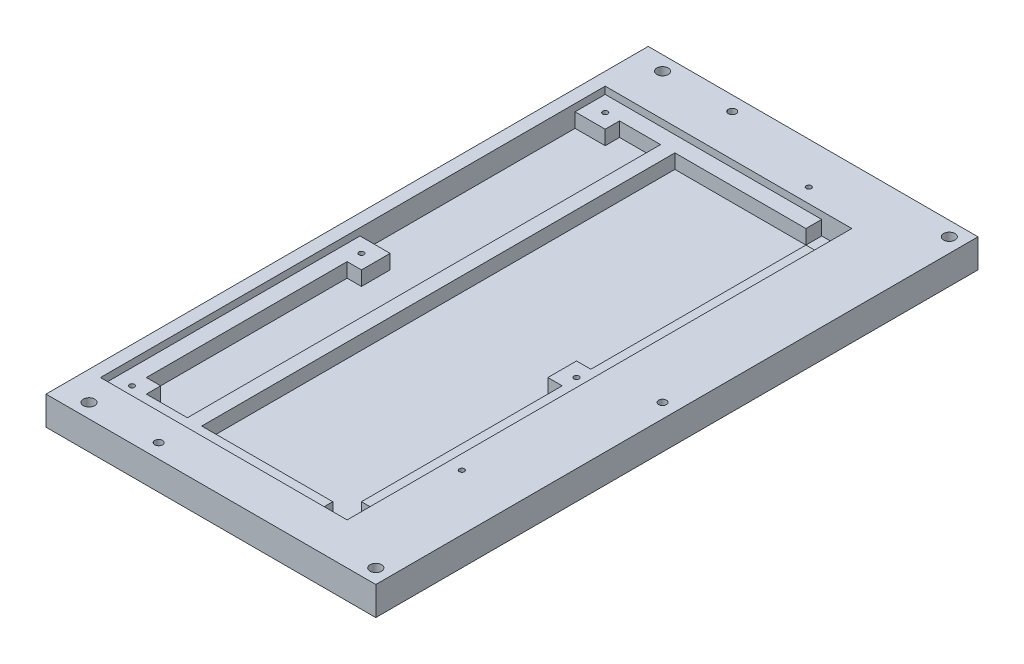
SolidWorks part; units mm, degrees
ref_plane "Front Plane" through (0, 0, 0) normal (0, 0, 1) x (1, 0, 0)
ref_plane "Top Plane" through (0, 0, 0) normal (0, 1, 0) x (1, 0, 0)
ref_plane "Right Plane" through (0, 0, 0) normal (1, 0, 0) x (0, 0, -1)
sketch "Sketch1" plane through (0, 0, 0) normal (0, 1, 0) x (1, 0, 0)
  line L1 (0, 0) -> (146.05, 0)
  line L2 (0, 0) -> (0, 266.7)
  line L3 (0, 266.7) -> (146.05, 266.7)
  line L4 (146.05, 0) -> (146.05, 266.7)
  dimension "D1" = 266.7
  dimension "D2" = 146.05
extrude "Boss-Extrude1" add sketch "Sketch1" along normal blind 12.7
sketch "Sketch2" plane through (0, 12.7, 0) normal (0, 1, 0) x (1, 0, 0)
  line L0 (146.05, 0) -> (146.05, 266.7) construction
  line L1 (5.715, 241.935) -> (114.935, 241.935)
  line L2 (5.715, 241.935) -> (5.715, 18.415)
  line L3 (5.715, 18.415) -> (114.935, 18.415)
  line L4 (114.935, 241.935) -> (114.935, 18.415)
  line L5 (0, 0) -> (146.05, 0) construction
  dimension "D1" = 223.52
  dimension "D2" = 109.22
  dimension "D3" = 31.115
  dimension "D4" = 18.415
extrude "Cut-Extrude1" cut sketch "Sketch2" against normal blind 3.175
sketch "Sketch3" plane through (0, 9.525, 0) normal (0, 1, 0) x (1, 0, 0)
  line L0 (19.05, 31.75) -> (19.05, 25.4)
  line L1 (19.05, 228.6) -> (19.05, 234.95)
  line L2 (19.05, 234.95) -> (37.211, 234.95)
  line L3 (43.561, 25.4) -> (101.6, 25.4)
  line L4 (101.6, 25.4) -> (101.6, 18.415)
  line L5 (43.561, 234.95) -> (101.6, 234.95)
  line L6 (107.95, 31.75) -> (107.95, 120.65)
  line L7 (101.6, 234.95) -> (101.6, 241.935)
  line L8 (107.95, 120.65) -> (101.6, 120.65)
  line L9 (101.6, 120.65) -> (101.6, 133.35)
  line L10 (101.6, 133.35) -> (107.95, 133.35)
  line L11 (107.95, 133.35) -> (107.95, 228.6)
  line L12 (101.6, 241.935) -> (114.935, 241.935)
  line L13 (114.935, 241.935) -> (5.715, 241.935) construction
  line L14 (101.6, 18.415) -> (114.935, 18.415)
  line L15 (114.935, 18.415) -> (114.935, 31.75)
  line L16 (114.935, 18.415) -> (114.935, 241.935) construction
  line L17 (114.935, 31.75) -> (107.95, 31.75)
  line L18 (19.05, 228.6) -> (5.715, 228.6)
  line L19 (5.715, 241.935) -> (5.715, 18.415) construction
  line L20 (5.715, 228.6) -> (5.715, 133.35)
  line L21 (5.715, 133.35) -> (19.05, 133.35)
  line L22 (19.05, 133.35) -> (19.05, 120.65)
  line L23 (19.05, 120.65) -> (12.7, 120.65)
  line L24 (12.7, 120.65) -> (12.7, 31.75)
  line L25 (12.7, 31.75) -> (19.05, 31.75)
  line L26 (19.05, 25.4) -> (37.211, 25.4)
  line L27 (37.211, 234.95) -> (37.211, 25.4)
  line L28 (114.935, 241.935) -> (114.935, 228.6)
  line L29 (43.561, 25.4) -> (43.561, 234.95)
  line L30 (114.935, 228.6) -> (107.95, 228.6)
  line L31 (5.715, 18.415) -> (114.935, 18.415) construction
  line L32 (5.715, 18.415) -> (114.935, 18.415) construction
  line L35 (114.935, 18.415) -> (114.935, 241.935) construction
  dimension "D3" = 6.985
  dimension "D4" = 13.335
  dimension "D5" = 13.335
  dimension "D6" = 6.35
  dimension "D7" = 6.35
  dimension "D8" = 13.335
  dimension "D9" = 12.7
  dimension "D10" = 12.7
  dimension "D11" = 6.35
  dimension "D12" = 31.496
  dimension "D13" = 13.335
  dimension "D14" = 95.25
  dimension "D15" = 13.335
  dimension "D16" = 6.35
  dimension "D17" = 6.985
  dimension "D18" = 6.985
  dimension "D19" = 6.985
  dimension "D20" = 6.35
  dimension "D21" = 6.35
  dimension "D22" = 13.335
  dimension "D23" = 88.9
  dimension "D24" = 6.985
  dimension "D25" = 6.985
extrude "Cut-Extrude2" cut sketch "Sketch3" against normal blind 6.35
hole_wizard "#4-40 Tapped Hole1" positions "Sketch5" profile "Sketch4" tap size "#4-40" standard "ANSI Inch"
sketch "Sketch5" plane through (0, 9.525, 0) normal (0, 1, 0) x (1, 0, 0)
  line L0 (19.05, 133.35) -> (19.05, 120.65) construction
  line L2 (101.6, 120.65) -> (101.6, 133.35) construction
  line L6 (19.05, 31.75) -> (19.05, 25.4) construction
  line L9 (19.05, 228.6) -> (5.715, 228.6) construction
  line L14 (12.7, 31.75) -> (19.05, 31.75) construction
  line L15 (19.05, 120.65) -> (12.7, 120.65) construction
  line L17 (107.95, 120.65) -> (101.6, 120.65) construction
  line L19 (19.05, 234.95) -> (19.05, 228.6) construction
  point P0 (12.7, 127)
  point P2 (107.95, 127)
  point P6 (12.7, 234.95)
  point P8 (12.7, 25.4)
  dimension "D1" = 6.35
  dimension "D2" = 6.35
  dimension "D3" = 6.35
  dimension "D4" = 6.35
  dimension "D7" = 6.35
  dimension "D8" = 6.35
  dimension "D9" = 6.35
  dimension "D10" = 6.35
sketch "Sketch4" plane through (12.7, 9.525, -127) normal (1, 0, 0) x (0, 0, 1)
  line L0 (0, 0) -> (0, 7.0292)
  line L1 (0, 7.0292) -> (1.1303, 6.35)
  line L2 (1.1303, 6.35) -> (1.1303, 0)
  line L5 (1.1303, 0) -> (0, 0)
  line L10 (0, 7.0292) -> (-1.1303, 6.35) construction
  line L11 (0, -6.35) -> (0, 107.95) construction
  dimension "Tap Drill Dia." = 2.2606
  dimension "Tap Drill Depth" = 6.35
  dimension "Drill Angle" = 118
cosmetic thread "Hole Thread2" parameters "D1"=5.588, "D2"=2.8448
cosmetic thread "Hole Thread3" parameters "D1"=5.588, "D2"=2.8448
cosmetic thread "Hole Thread5" parameters "D1"=5.588, "D2"=2.8448
cosmetic thread "Hole Thread6" parameters "D1"=5.588, "D2"=2.8448
hole_wizard "#8 (0.199) Diameter Hole2" positions "Sketch9" profile "Sketch8" hole size "#8" standard "ANSI Inch" end condition through all
sketch "Sketch9" plane through (0, 12.7, 0) normal (0, 1, 0) x (1, 0, 0)
  line L0 (0, 0) -> (146.05, 0) construction
  line L1 (146.05, 0) -> (146.05, 266.7) construction
  line L2 (146.05, 266.7) -> (0, 266.7) construction
  line L3 (0, 266.7) -> (0, 0) construction
  point P0 (12.7, 6.35)
  point P2 (139.7, 6.35)
  point P4 (139.7, 260.35)
  point P6 (12.7, 260.35)
  dimension "D1" = 6.35
  dimension "D2" = 6.35
  dimension "D3" = 6.35
  dimension "D4" = 6.35
  dimension "D5" = 6.35
  dimension "D6" = 6.35
  dimension "D7" = 12.7
  dimension "D8" = 12.7
sketch "Sketch8" plane through (12.7, 12.7, -6.35) normal (1, 0, 0) x (0, 0, 1)
  line L0 (0, 0) -> (0, 12.7)
  line L1 (0, 12.7) -> (2.5273, 12.7)
  line L2 (2.5273, 12.7) -> (2.5273, 0)
  line L5 (2.5273, 0) -> (0, 0)
  line L11 (0, -6.35) -> (0, 107.95) construction
  dimension "Thru Hole Dia." = 5.0546
  dimension "Thru Hole Depth" = 12.7
hole_wizard "#8-32 Tapped Hole1" positions "Sketch11" profile "Sketch12" tap size "#8-32" standard "ANSI Inch"
sketch "Sketch11" plane through (0, 12.7, 0) normal (0, 1, 0) x (1, 0, 0)
  line L0 (37.211, 25.4) -> (37.211, 234.95) construction
  line L1 (146.05, 266.7) -> (0, 266.7) construction
  line L2 (0, 0) -> (146.05, 0) construction
  line L3 (146.05, 0) -> (146.05, 266.7) construction
  point P0 (43.561, 6.35)
  point P2 (43.561, 260.35)
  point P11 (139.7, 133.35)
  dimension "D1" = 6.35
  dimension "D2" = 6.35
  dimension "D3" = 6.35
  dimension "D4" = 6.35
  dimension "D5" = 6.35
  dimension "D6" = 133.35
cosmetic thread "Hole Thread7" parameters "D1"=5.588, "D2"=4.1656
cosmetic thread "Hole Thread8" parameters "D1"=5.588, "D2"=4.1656
cosmetic thread "Hole Thread9" parameters "D1"=5.588, "D2"=4.1656
sketch "Sketch12" plane through (43.561, 12.7, -6.35) normal (1, 0, 0) x (0, 0, 1)
  line L0 (0, 0) -> (0, 10.5628)
  line L1 (0, 10.5628) -> (1.7272, 9.525)
  line L2 (1.7272, 9.525) -> (1.7272, 0)
  line L5 (1.7272, 0) -> (0, 0)
  line L10 (0, 10.5628) -> (-1.7272, 9.525) construction
  line L11 (0, -6.35) -> (0, 107.95) construction
  dimension "Tap Drill Dia." = 3.4544
  dimension "Tap Drill Depth" = 9.525
  dimension "Drill Angle" = 118
hole_wizard "#4-40 Tapped Hole2" positions "Sketch14" profile "Sketch15" tap size "#4-40" standard "ANSI Inch"
sketch "Sketch14" plane through (0, 12.7, 0) normal (0, 1, 0) x (1, 0, 0)
  line L0 (114.935, 18.415) -> (114.935, 241.935) construction
  line L1 (114.935, 241.935) -> (5.715, 241.935) construction
  line L2 (5.715, 18.415) -> (114.935, 18.415) construction
  point P0 (89.535, 248.285)
  point P2 (121.285, 62.865)
  dimension "D1" = 6.35
  dimension "D2" = 6.35
  dimension "D3" = 44.45
  dimension "D4" = 25.4
sketch "Sketch15" plane through (89.535, 12.7, -248.285) normal (1, 0, 0) x (0, 0, 1)
  line L0 (0, 0) -> (0, 10.3312)
  line L1 (0, 10.3312) -> (1.1303, 9.652)
  line L2 (1.1303, 9.652) -> (1.1303, 0)
  line L5 (1.1303, 0) -> (0, 0)
  line L10 (0, 10.3312) -> (-1.1303, 9.652) construction
  line L11 (0, -6.35) -> (0, 107.95) construction
  dimension "Tap Drill Dia." = 2.2606
  dimension "Tap Drill Depth" = 9.652
  dimension "Drill Angle" = 118
cosmetic thread "Hole Thread10" parameters "D1"=5.588, "D2"=2.8448
cosmetic thread "Hole Thread11" parameters "D1"=5.588, "D2"=2.8448
